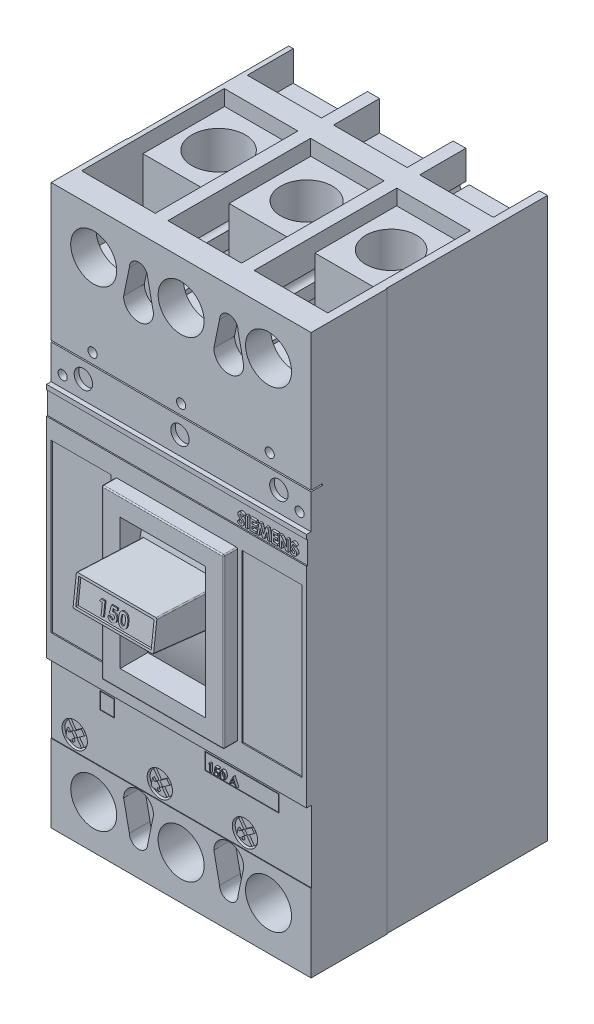
SolidWorks part; units mm, degrees
ref_plane "Alzado" through (0, 0, 0) normal (0, 0, 1) x (1, 0, 0)
ref_plane "Planta" through (0, 0, 0) normal (0, 1, 0) x (1, 0, 0)
ref_plane "Vista lateral" through (0, 0, 0) normal (1, 0, 0) x (0, 0, -1)
sketch "Croquis1" plane through (0, 0, 0) normal (0, 0, 1) x (1, 0, 0)
  line L1 (-56.5, -121.5) -> (56.5, -121.5)
  line L2 (-56.5, -121.5) -> (-56.5, 121.5)
  line L3 (-56.5, 121.5) -> (56.5, 121.5)
  line L4 (56.5, -121.5) -> (56.5, 121.5)
  line L5 (-56.5, -121.5) -> (56.5, 121.5) construction
  line L6 (-56.5, 121.5) -> (56.5, -121.5) construction
  point P0 (0, 0)
  dimension "D1" = 113
  dimension "D2" = 243
extrude "Saliente-Extruir1" add sketch "Croquis1" along normal blind 105
sketch "Croquis2" plane through (0, 0, 105) normal (0, 0, 1) x (1, 0, 0)
  line L0 (56.5, -121.5) -> (56.5, -56.5)
  line L1 (56.5, -121.5) -> (56.5, 121.5) construction
  line L2 (56.5, -56.5) -> (-56.5, -56.5)
  line L3 (-56.5, 121.5) -> (-56.5, -121.5) construction
  line L4 (-56.5, -56.5) -> (-56.5, -121.5)
  line L5 (-56.5, -121.5) -> (56.5, -121.5)
  dimension "D1" = 65
extrude "Cortar-Extruir1" cut sketch "Croquis2" against normal blind 2
sketch "Croquis3" plane through (0, 0, 105) normal (0, 0, 1) x (1, 0, 0)
  line L0 (-56.5, 121.5) -> (-56.5, 46.5)
  line L1 (-56.5, 121.5) -> (-56.5, -56.5) construction
  line L2 (-56.5, 46.5) -> (56.5, 46.5)
  line L3 (56.5, -56.5) -> (56.5, 121.5) construction
  line L4 (56.5, 46.5) -> (56.5, 121.5)
  line L5 (56.5, 121.5) -> (-56.5, 121.5)
  dimension "D1" = 75
extrude "Cortar-Extruir2" cut sketch "Croquis3" against normal blind 2
sketch "Croquis4" plane through (0, 0, 105) normal (0, 0, 1) x (1, 0, 0)
  line L0 (56.5, -56.5) -> (56.5, 46.5) construction
  line L1 (-26.5, -46.5) -> (26.5, -46.5)
  line L2 (-26.5, -46.5) -> (-26.5, 26.5)
  line L3 (-26.5, 26.5) -> (26.5, 26.5)
  line L4 (26.5, -46.5) -> (26.5, 26.5)
  line L5 (-26.5, -46.5) -> (26.5, 26.5) construction
  line L6 (-26.5, 26.5) -> (26.5, -46.5) construction
  line L7 (-56.5, 46.5) -> (56.5, 46.5) construction
  line L8 (-56.5, 46.5) -> (-56.5, -56.5) construction
  line L9 (56.5, -56.5) -> (-56.5, -56.5) construction
  point P0 (0, -10)
  dimension "D1" = 30
  dimension "D2" = 20
  dimension "D3" = 30
  dimension "D4" = 10
extrude "Saliente-Extruir2" add sketch "Croquis4" along normal blind 6
sketch "Croquis5" plane through (0, 0, 111) normal (0, 0, 1) x (1, 0, 0)
  line L0 (26.5, -46.5) -> (26.5, 26.5) construction
  line L1 (-18.5, -38.5) -> (18.5, -38.5)
  line L2 (-18.5, -38.5) -> (-18.5, 18.5)
  line L3 (-18.5, 18.5) -> (18.5, 18.5)
  line L4 (18.5, -38.5) -> (18.5, 18.5)
  line L5 (-18.5, -38.5) -> (18.5, 18.5) construction
  line L6 (-18.5, 18.5) -> (18.5, -38.5) construction
  line L7 (26.5, 26.5) -> (-26.5, 26.5) construction
  line L8 (-26.5, 26.5) -> (-26.5, -46.5) construction
  line L9 (-26.5, -46.5) -> (26.5, -46.5) construction
  point P0 (0, -10)
  point P11 (-18.5, -10)
  dimension "D1" = 8
  dimension "D2" = 8
  dimension "D3" = 8
  dimension "D4" = 8
extrude "Cortar-Extruir3" cut sketch "Croquis5" against normal blind 7
sketch "Croquis6" plane through (-18.5, 0, 0) normal (1, 0, 0) x (0, 0, -1)
  line L0 (-104, 18.5) -> (-99, 18.5)
  line L1 (-104, -38.5) -> (-99, -38.5)
  line L2 (-104, 18.5) -> (-106.9692, 18.5)
  line L3 (-106.9692, 18.5) -> (-106.9692, -38.5)
  line L4 (-106.9692, -38.5) -> (-104, -38.5)
  arc A0 (-99, -38.5) -> (-99, 18.5) centre (-20.275, -10) cw
  dimension "D1" = 5
extrude "Cortar-Extruir4" cut sketch "Croquis6" along normal up to surface (37 mm away) up to face at (18.5, -10, 107.5)
sketch "Croquis7" plane through (-18.5, 0, 0) normal (1, 0, 0) x (0, 0, -1)
  line L0 (-102.2276, 7.1359) -> (-131, 8.458)
  line L1 (-111, -46.5) -> (-111, 26.5) construction
  line L2 (-131, 8.458) -> (-132.497, -4.4555)
  line L3 (-132.497, -4.4555) -> (-103.9701, -7.7626)
  arc A0 (-99, 18.5) -> (-99, -38.5) centre (-20.275, -10) ccw construction
  arc A1 (-102.2276, 7.1359) -> (-103.9701, -7.7626) centre (-20.275, -10) ccw
  dimension "D1" = 20
  dimension "D2" = 13
  dimension "D3" = 15
extrude "Saliente-Extruir3" add sketch "Croquis7" along normal up to surface (37 mm away) up to face at (18.5, -10, 106.25)
sketch "Croquis9" plane through (18.5, 0, 0) normal (1, 0, 0) x (0, 0, -1)
  line L0 (-131, 8.458) -> (-102.2276, 7.1359)
  line L1 (-131, 8.458) -> (-132.497, -4.4555)
  line L2 (-132.497, -4.4555) -> (-103.9701, -7.7626)
  arc A0 (-103.9701, -7.7626) -> (-102.2276, 7.1359) centre (-38.2725, -7.8951) cw
extrude "Cortar-Extruir5" cut sketch "Croquis9" against normal blind 1
sketch "Croquis10" plane through (-18.5, 0, 0) normal (-1, 0, 0) x (0, 0, 1)
  line L0 (102.2276, 7.1359) -> (131, 8.458)
  line L1 (131, 8.458) -> (132.497, -4.4555)
  line L2 (132.497, -4.4555) -> (103.9701, -7.7626)
  arc A0 (103.9701, -7.7626) -> (102.2276, 7.1359) centre (38.2725, -7.8951) ccw
extrude "Cortar-Extruir6" cut sketch "Croquis10" against normal blind 1
sketch "Croquis11" plane through (0, 15.0972, 130.2303) normal (0, 0.1152, 0.9933) x (1, 0, 0)
  line L1 (-16.3625, -18.6242) -> (16.3625, -18.6242)
  line L2 (-16.3625, -18.6242) -> (-16.3625, -7.7431)
  line L3 (-16.3625, -7.7431) -> (16.3625, -7.7431)
  line L4 (16.3625, -18.6242) -> (16.3625, -7.7431)
  line L5 (-16.3625, -18.6242) -> (16.3625, -7.7431) construction
  line L6 (-16.3625, -7.7431) -> (16.3625, -18.6242) construction
  point P0 (0, -13.1836)
extrude "Cortar-Extruir7" cut sketch "Croquis11" against normal blind 1
fillet "Redondeo1" radius 0.5 4 edges at (17.5, -6.109, 118.2336) (17.5, 7.7969, 116.6138) (-17.5, -6.109, 118.2336) (-17.5, 7.7969, 116.6138)
sketch "Croquis12" plane through (0, 14.982, 129.237) normal (0, 0.1152, 0.9933) x (1, 0, 0)
  line L0 (-10.1967, -17.2783) -> (10.7691, -17.2783) construction
  text T0 " 150" font "Century Gothic" height in points 22
extrude "Saliente-Extruir4" add sketch "Croquis12" along normal blind 0.5
fillet "Redondeo2" radius 0.5 8 edges at (-26.5, -46.5, 108) (26.5, -46.5, 108) (0, -46.5, 111) (26.5, -10, 111) (26.5, 26.5, 108) (0, 26.5, 111) (-26.5, -10, 111) (-26.5, 26.5, 108)
sketch "Croquis13" plane through (0, 0, 103) normal (0, 0, 1) x (1, 0, 0)
  line L0 (56.5, 121.5) -> (-56.5, 121.5) construction
  line L1 (56.5, 121.5) -> (56.5, -121.5) construction
  line L2 (56.5, 0) -> (-56.5, 0) construction
  line L3 (-56.5, 46.5) -> (-56.5, -56.5) construction
  circle A0 centre (0, 102.5) radius 10
  circle A1 centre (-38, 102.5) radius 10
  circle A2 centre (38, 102.5) radius 10
  circle A3 centre (38, -102.5) radius 10
  circle A4 centre (-38, -102.5) radius 10
  circle A5 centre (0, -102.5) radius 10
  dimension "D1" = 20
  dimension "D3" = 38
  dimension "D4" = 20
  dimension "D7" = 38
  dimension "D8" = 20
  dimension "D2" = 19
  dimension "D5" = 19
  dimension "D6" = 19
extrude "Cortar-Extruir8" cut sketch "Croquis13" against normal blind 39
sketch "Croquis14" plane through (0, 0, 103) normal (0, 0, 1) x (1, 0, 0)
  line L0 (-56.5, 46.5) -> (56.5, 46.5) construction
  line L1 (-56.5, 121.5) -> (-56.5, 46.5) construction
  line L2 (-25, 94.5) -> (-22.5, 106.5)
  line L3 (-12, 94.5) -> (-14.5, 106.5)
  line L4 (14.2234, 94.5) -> (16.7234, 106.5)
  line L5 (24.7234, 106.5) -> (27.2234, 94.5)
  line L6 (56.5, 121.5) -> (56.5, -121.5) construction
  line L7 (56.5, 0) -> (-56.5, 0) construction
  line L8 (-56.5, 46.5) -> (-56.5, -56.5) construction
  line L9 (24.7234, -106.5) -> (27.2234, -94.5)
  line L10 (14.2234, -94.5) -> (16.7234, -106.5)
  line L11 (-12, -94.5) -> (-14.5, -106.5)
  line L12 (-25, -94.5) -> (-22.5, -106.5)
  arc A0 (-25, 94.5) -> (-12, 94.5) centre (-18.5, 94.5) ccw
  arc A1 (14.2234, 94.5) -> (27.2234, 94.5) centre (20.7234, 94.5) ccw
  arc A2 (-14.5, 106.5) -> (-22.5, 106.5) centre (-18.5, 106.5) ccw
  arc A3 (24.7234, 106.5) -> (16.7234, 106.5) centre (20.7234, 106.5) ccw
  arc A4 (24.7234, -106.5) -> (16.7234, -106.5) centre (20.7234, -106.5) cw
  arc A5 (-14.5, -106.5) -> (-22.5, -106.5) centre (-18.5, -106.5) cw
  arc A6 (14.2234, -94.5) -> (27.2234, -94.5) centre (20.7234, -94.5) cw
  arc A7 (-25, -94.5) -> (-12, -94.5) centre (-18.5, -94.5) cw
  dimension "D3" = 48
  dimension "D4" = 13
  dimension "D5" = 13
  dimension "D8" = 8
  dimension "D9" = 8
  dimension "D1" = 48
  dimension "D2" = 38
  dimension "D6" = 12
  dimension "D7" = 12
extrude "Cortar-Extruir9" cut sketch "Croquis14" against normal blind 9
sketch "Croquis15" plane through (0, 0, 94) normal (0, 0, 1) x (1, 0, 0)
  circle A0 centre (-18.5, 94.5) radius 3.5
  circle A1 centre (20.7234, 94.5) radius 3.5
  circle A2 centre (-18.5, 106.5) radius 2.5
  circle A3 centre (20.7234, 106.5) radius 2.5
  dimension "D1" = 7
  dimension "D2" = 7
  dimension "D3" = 5
  dimension "D4" = 5
extrude "Cortar-Extruir10" cut sketch "Croquis15" against normal up to surface (94 mm away) up to face at (0, 0, 0)
sketch "Croquis16" plane through (0, 0, 94) normal (0, 0, 1) x (1, 0, 0)
  circle A0 centre (-18.5, -94.5) radius 3.5
  circle A1 centre (-18.5, -106.5) radius 2.5
  circle A4 centre (20.7234, -94.5) radius 3.5
  circle A5 centre (20.7234, -106.5) radius 2.5
  dimension "D1" = 7
  dimension "D2" = 5
  dimension "D3" = 7
  dimension "D4" = 5
extrude "Cortar-Extruir11" cut sketch "Croquis16" against normal up to surface (94 mm away) up to face at (17.2234, 94.5, 0)
sketch "Croquis17" plane through (0, 0, 103) normal (0, 0, 1) x (1, 0, 0)
  line L0 (-56.5, 121.5) -> (-56.5, 46.5) construction
  line L1 (-56.5, 46.5) -> (56.5, 46.5) construction
  line L2 (56.5, 46.5) -> (56.5, 121.5) construction
  circle A0 centre (-42.5, 54.5) radius 4
  circle A1 centre (-0.5, 54.5) radius 4
  circle A2 centre (42.5, 55.2532) radius 4
  dimension "D1" = 8
  dimension "D4" = 8
  dimension "D6" = 42
  dimension "D7" = 8
  dimension "D2" = 14
  dimension "D3" = 8
  dimension "D5" = 8
  dimension "D8" = 14
extrude "Cortar-Extruir12" cut sketch "Croquis17" against normal blind 2
sketch "Croquis18" plane through (0, 0, 103) normal (0, 0, 1) x (1, 0, 0)
  line L0 (-56.5, 46.5) -> (56.5, 46.5) construction
  line L1 (-56.5, 121.5) -> (-56.5, 46.5) construction
  line L2 (56.5, 46.5) -> (56.5, 121.5) construction
  circle A0 centre (-51.5, 51.5) radius 2
  circle A1 centre (51.5, 51.5) radius 2
  circle A2 centre (0, 66.5) radius 2
  circle A3 centre (38.5, 67.2532) radius 2
  circle A4 centre (-38.5, 66.5) radius 2
  circle A5 centre (-0.5, 54.5) radius 4 construction
  circle A6 centre (42.5, 55.2532) radius 4 construction
  circle A7 centre (-42.5, 54.5) radius 4 construction
  dimension "D1" = 4
  dimension "D2" = 4
  dimension "D4" = 5
  dimension "D7" = 4
  dimension "D8" = 4
  dimension "D9" = 4
  dimension "D10" = 12
  dimension "D11" = 12
  dimension "D13" = 12
  dimension "D14" = 18
  dimension "D3" = 5
  dimension "D5" = 5
  dimension "D6" = 5
  dimension "D12" = 18
extrude "Cortar-Extruir13" cut sketch "Croquis18" against normal blind 10
sketch "Croquis19" plane through (0, 0, 103) normal (0, 0, 1) x (1, 0, 0)
  line L0 (-56.5, 61.5) -> (56.5, 61.5)
  line L1 (-56.5, 121.5) -> (-56.5, 46.5) construction
  line L2 (56.5, 46.5) -> (56.5, 121.5) construction
  line L3 (56.5, 61.5) -> (56.5, 62.1)
  line L4 (56.5, 62.1) -> (-56.5, 62.1)
  line L5 (-56.5, 62.1) -> (-56.5, 61.5)
  dimension "D1" = 15
  dimension "D2" = 0.6
extrude "Cortar-Extruir14" cut sketch "Croquis19" against normal blind 5
sketch "Croquis20" plane through (0, 0, 103) normal (0, 0, 1) x (1, 0, 0)
  line L0 (-56.5, -56.5) -> (-56.5, -121.5) construction
  circle A0 centre (-9.5, -81.5) radius 5.5
  circle A1 centre (27.5, -81.5) radius 5.5
  circle A2 centre (-46.5, -81.5) radius 5.5
  circle A3 centre (-38, -102.5) radius 10 construction
  circle A4 centre (0, -102.5) radius 10 construction
  circle A5 centre (38, -102.5) radius 10 construction
  dimension "D1" = 11
  dimension "D3" = 21
  dimension "D4" = 11
  dimension "D5" = 37
  dimension "D6" = 21
  dimension "D7" = 11
  dimension "D8" = 37
  dimension "D9" = 21
  dimension "D2" = 10
extrude "Cortar-Extruir15" cut sketch "Croquis20" against normal blind 5
sketch "Croquis21" plane through (0, 0, 98) normal (0, 0, 1) x (1, 0, 0)
  circle A0 centre (-46.5, -81.5) radius 5
  circle A1 centre (-9.5, -81.5) radius 5
  circle A2 centre (27.5, -81.5) radius 5
  dimension "D1" = 10
  dimension "D2" = 10
  dimension "D3" = 10
extrude "Saliente-Extruir5" add sketch "Croquis21" along normal blind 4
sketch "Croquis22" plane through (0, 0, 102) normal (0, 0, 1) x (1, 0, 0)
  line L0 (-49.4105, -77.4344) -> (-43.5895, -85.5656) construction
  line L1 (-12.4105, -77.4344) -> (-6.5895, -85.5656) construction
  line L2 (24.5895, -77.4344) -> (30.4105, -85.5656) construction
  line L3 (-49.9553, -77.886) -> (-44.1926, -85.9358)
  line L4 (-48.8074, -77.0642) -> (-43.0447, -85.114)
  line L5 (-12.9553, -77.886) -> (-7.1926, -85.9358)
  line L6 (-11.8074, -77.0642) -> (-6.0447, -85.114)
  line L7 (24.0447, -77.886) -> (29.8074, -85.9358)
  line L8 (25.1926, -77.0642) -> (30.9553, -85.114)
  circle A0 centre (-46.5, -81.5) radius 5 construction
  circle A1 centre (-9.5, -81.5) radius 5 construction
  circle A2 centre (27.5, -81.5) radius 5 construction
  circle A3 centre (27.5, -81.5) radius 5 construction
  circle A7 centre (-46.5, -81.5) radius 5 construction
  arc A8 (-49.9553, -77.886) -> (-48.8074, -77.0642) centre (-46.5, -81.5) cw
  arc A9 (-44.1926, -85.9358) -> (-43.0447, -85.114) centre (-46.5, -81.5) ccw
  circle A12 centre (-9.5, -81.5) radius 5 construction
  arc A13 (-12.9553, -77.886) -> (-11.8074, -77.0642) centre (-9.5, -81.5) cw
  arc A14 (-7.1926, -85.9358) -> (-6.0447, -85.114) centre (-9.5, -81.5) ccw
  arc A15 (24.0447, -77.886) -> (25.1926, -77.0642) centre (27.5, -81.5) cw
  arc A16 (29.8074, -85.9358) -> (30.9553, -85.114) centre (27.5, -81.5) ccw
extrude "Cortar-Extruir16" cut sketch "Croquis22" against normal blind 2
sketch "Croquis23" plane through (0, 0, 102) normal (0, 0, 1) x (1, 0, 0)
  line L0 (-47.7579, -80.9555) -> (-49.0924, -81.9109)
  line L1 (-49.9553, -77.886) -> (-44.1926, -85.9358) construction
  line L2 (-49.0924, -81.9109) -> (-49.8983, -80.7851)
  line L3 (-46.407, -82.8426) -> (-47.7579, -83.8097)
  line L4 (-49.9553, -77.886) -> (-44.1926, -85.9358) construction
  line L5 (-47.7579, -83.8097) -> (-47.0824, -84.7532)
  line L6 (-47.0824, -84.7532) -> (-50.3001, -84.2204)
  line L7 (-50.3001, -84.2204) -> (-49.8983, -80.7851)
  line L8 (-46.61, -80.1338) -> (-43.6216, -77.9944)
  line L9 (-43.0447, -85.114) -> (-48.8074, -77.0642) construction
  line L10 (-43.6216, -77.9944) -> (-42.2707, -79.8814)
  line L11 (-42.2707, -79.8814) -> (-45.2591, -82.0208)
  line L12 (-45.2591, -82.0208) -> (-46.61, -80.1338)
  line L13 (-46.407, -82.8426) -> (-47.7579, -80.9555)
  line L14 (-10.6623, -81.0891) -> (-11.8102, -81.9109)
  line L15 (-12.9553, -77.886) -> (-7.1926, -85.9358) construction
  line L16 (-11.8102, -81.9109) -> (-12.3985, -81.0891)
  line L17 (-9.407, -82.8426) -> (-10.6623, -83.7412)
  line L18 (-12.9553, -77.886) -> (-7.1926, -85.9358) construction
  line L19 (-10.6623, -83.7412) -> (-9.9378, -84.7532)
  line L20 (-9.9378, -84.7532) -> (-13.2729, -84.201)
  line L21 (-13.2729, -84.201) -> (-12.7073, -80.7851)
  line L22 (-12.7073, -80.7851) -> (-12.3985, -81.0891)
  line L23 (-9.5143, -80.2673) -> (-6.4755, -78.0918)
  line L24 (-6.0447, -85.114) -> (-11.8074, -77.0642) construction
  line L25 (-6.4755, -78.0918) -> (-5.1943, -79.8814)
  line L26 (-5.1943, -79.8814) -> (-8.2332, -82.0569)
  line L27 (-6.0447, -85.114) -> (-11.8074, -77.0642) construction
  line L28 (-8.2332, -82.0569) -> (-9.5143, -80.2673)
  line L29 (-9.407, -82.8426) -> (-10.6623, -81.0891)
  line L30 (26.3261, -81.0729) -> (25.0665, -81.9746)
  line L31 (24.0447, -77.886) -> (29.8074, -85.9358) construction
  line L32 (25.0665, -81.9746) -> (24.4849, -81.1621)
  line L33 (27.454, -82.6484) -> (26.1033, -83.6153)
  line L34 (24.0447, -77.886) -> (29.8074, -85.9358) construction
  line L35 (26.1033, -83.6153) -> (26.8154, -84.61)
  line L36 (26.8154, -84.61) -> (23.9977, -84.0073)
  line L37 (23.9977, -84.0073) -> (24.4849, -81.1621)
  line L38 (27.454, -80.2231) -> (30.4311, -78.0918)
  line L39 (30.9553, -85.114) -> (25.1926, -77.0642) construction
  line L40 (30.4311, -78.0918) -> (31.579, -79.6953)
  line L41 (31.579, -79.6953) -> (28.6019, -81.8266)
  line L42 (28.6019, -81.8266) -> (27.454, -80.2231)
  line L43 (27.454, -82.6484) -> (26.3261, -81.0729)
extrude "Saliente-Extruir6" add sketch "Croquis23" along normal blind 1
sketch "Croquis24" plane through (0, 0, 105) normal (0, 0, 1) x (1, 0, 0)
  line L0 (-56.5, 44.5) -> (56.5, 44.5)
  line L1 (-56.5, 46.5) -> (-56.5, -56.5) construction
  line L2 (56.5, -56.5) -> (56.5, 46.5) construction
  line L3 (56.5, 44.5) -> (56.5, 34.5)
  line L4 (56.5, 34.5) -> (-56.5, 34.5)
  line L5 (-56.5, 34.5) -> (-56.5, 44.5)
  line L6 (-56.5, 46.5) -> (56.5, 46.5) construction
  line L7 (28.5, 26.5) -> (54.5, 26.5)
  line L8 (54.5, 26.5) -> (54.5, -46)
  line L9 (54.5, -46) -> (28.5, -46)
  line L10 (28.5, -46) -> (28.5, 26.5)
  line L11 (-28.5, 26.5) -> (-28.5, -46)
  line L12 (-28.5, -46) -> (-54.5, -46)
  line L13 (-54.5, -46) -> (-54.5, 26.5)
  line L14 (-54.5, 26.5) -> (-28.5, 26.5)
  line L15 (-26.5, 26) -> (-26.5, -46) construction
  line L16 (26.5, 26) -> (26.5, -46) construction
  arc A0 (26, -46.5) -> (26.5, -46) centre (26, -46) ccw construction
  dimension "D9" = 0
  dimension "D1" = 2
  dimension "D2" = 10
  dimension "D3" = 2
  dimension "D4" = 0
  dimension "D5" = 0
  dimension "D6" = 2
  dimension "D7" = 2
  dimension "D8" = 2
  dimension "D10" = 0
extrude "Cortar-Extruir17" cut sketch "Croquis24" against normal blind 0.5
sketch "Croquis25" plane through (0, 0, 103) normal (0, 0, 1) x (1, 0, 0)
  line L0 (-56.5, -87.75) -> (56.5, -87.75)
  line L1 (-56.5, -56.5) -> (-56.5, -121.5) construction
  line L2 (56.5, -121.5) -> (56.5, -56.5) construction
  line L3 (-56.5, -121.5) -> (56.5, -121.5) construction
  line L4 (-56.5, -87.75) -> (-56.5, -56.5)
  line L5 (-56.5, -56.5) -> (56.5, -56.5)
  line L6 (56.5, -56.5) -> (56.5, -87.75)
  dimension "D1" = 33.75
extrude "Cortar-Extruir18" cut sketch "Croquis25" against normal blind 0.25
sketch "Croquis26" plane through (56.5, 0, 0) normal (1, 0, 0) x (0, 0, -1)
  line L0 (-70, 121.5) -> (-70, -121.5)
  line L1 (-103, 121.5) -> (0, 121.5) construction
  line L2 (-103, -121.5) -> (0, -121.5) construction
  line L3 (-103, 62.1) -> (-103, 121.5) construction
  line L4 (0, -121.5) -> (0, 121.5) construction
  line L5 (-70, 121.5) -> (0, 121.5)
  line L6 (0, 121.5) -> (0, -121.5)
  line L7 (0, -121.5) -> (-70, -121.5)
  dimension "D1" = 33
  dimension "D2" = 70
extrude "Cortar-Extruir19" cut sketch "Croquis26" against normal blind 0.25
sketch "Croquis28" plane through (-56.5, 0, 0) normal (-1, 0, 0) x (0, 0, 1)
  line L0 (70, 121.5) -> (70, -121.5)
  line L1 (103, -121.5) -> (0, -121.5) construction
  line L2 (70, 121.5) -> (0, 121.5)
  line L3 (0, 121.5) -> (0, -121.5)
  line L4 (0, -121.5) -> (70, -121.5)
extrude "Cortar-Extruir20" cut sketch "Croquis28" against normal blind 0.25
sketch "Croquis29" plane through (0, 0, 102.75) normal (0, 0, 1) x (1, 0, 0)
  line L1 (10.1285, -66.6911) -> (42.3006, -66.6911)
  line L2 (10.1285, -66.6911) -> (10.1285, -59.3793)
  line L3 (10.1285, -59.3793) -> (42.3006, -59.3793)
  line L4 (42.3006, -66.6911) -> (42.3006, -59.3793)
  line L5 (10.1285, -66.6911) -> (42.3006, -59.3793) construction
  line L6 (10.1285, -59.3793) -> (42.3006, -66.6911) construction
  line L7 (-35.4486, -66.6911) -> (-29.1117, -66.6911)
  line L8 (-35.4486, -66.6911) -> (-35.4486, -59.3793)
  line L9 (-35.4486, -59.3793) -> (-29.1117, -59.3793)
  line L10 (-29.1117, -66.6911) -> (-29.1117, -59.3793)
  line L11 (-35.4486, -66.6911) -> (-29.1117, -59.3793) construction
  line L12 (-35.4486, -59.3793) -> (-29.1117, -66.6911) construction
  point P0 (26.2146, -63.0352)
  point P5 (-32.2802, -63.0352)
extrude "Cortar-Extruir21" cut sketch "Croquis29" against normal blind 4
sketch "Croquis30" plane through (0, 0, 98.75) normal (0, 0, 1) x (1, 0, 0)
  line L1 (10.3184, -66.4658) -> (42.1108, -66.4658)
  line L2 (10.3184, -66.4658) -> (10.3184, -59.6046)
  line L3 (10.3184, -59.6046) -> (42.1108, -59.6046)
  line L4 (42.1108, -66.4658) -> (42.1108, -59.6046)
  line L5 (10.3184, -66.4658) -> (42.1108, -59.6046) construction
  line L6 (10.3184, -59.6046) -> (42.1108, -66.4658) construction
  line L7 (-35.2213, -66.4658) -> (-29.3391, -66.4658)
  line L8 (-35.2213, -66.4658) -> (-35.2213, -59.6046)
  line L9 (-35.2213, -59.6046) -> (-29.3391, -59.6046)
  line L10 (-29.3391, -66.4658) -> (-29.3391, -59.6046)
  line L11 (-35.2213, -66.4658) -> (-29.3391, -59.6046) construction
  line L12 (-35.2213, -59.6046) -> (-29.3391, -66.4658) construction
  point P0 (26.2146, -63.0352)
  point P5 (-32.2802, -63.0352)
extrude "Saliente-Extruir7" add sketch "Croquis30" along normal blind 4
sketch "Croquis32" plane through (0, 121.5, 0) normal (0, 1, 0) x (1, 0, 0)
  line L0 (-54.25, -92) -> (-54.25, -30)
  line L1 (-54.25, -92) -> (-22.25, -92)
  line L2 (-22.25, -92) -> (-22.25, -30)
  line L5 (56.5, -103) -> (-56.5, -103) construction
  line L6 (-16.75, -92) -> (-16.75, -30)
  line L7 (-16.75, -92) -> (15.25, -92)
  line L8 (15.25, -92) -> (15.25, -30)
  line L9 (20.75, -92) -> (20.75, -30)
  line L10 (20.75, -92) -> (52.75, -92)
  line L11 (52.75, -92) -> (52.75, -30)
  line L12 (-54.25, -30) -> (-22.25, -30)
  line L13 (15.25, -30) -> (-16.75, -30)
  line L14 (52.75, -30) -> (20.75, -30)
  dimension "D1" = 32
  dimension "D3" = 11
  dimension "D4" = 32
  dimension "D5" = 5.5
  dimension "D6" = 32
  dimension "D9" = 62
  dimension "D10" = 62
  dimension "D12" = 62
extrude "Cortar-Extruir22" cut sketch "Croquis32" against normal blind 32
sketch "Croquis33" plane through (0, 121.5, 0) normal (0, 1, 0) x (1, 0, 0)
  line L0 (-54.25, -20) -> (-22, -20)
  line L1 (-22, 0) -> (-22, -94) construction
  line L2 (-22, -20) -> (-22, 0)
  line L3 (-22, 0) -> (-54.25, 0)
  line L4 (56.25, 0) -> (-56.25, 0) construction
  line L5 (-54.25, 0) -> (-54.25, -20)
  line L6 (-22.25, -30) -> (-54.25, -30) construction
  line L7 (-16.75, -20) -> (15.25, -20)
  line L8 (15.25, -20) -> (15.25, 0)
  line L9 (15.25, 0) -> (-16.75, 0)
  line L10 (-16.75, 0) -> (-16.75, -20)
  line L11 (52.75, -20) -> (20.75, -20)
  line L12 (20.75, -20) -> (20.75, 0)
  line L13 (20.75, 0) -> (52.75, 0)
  line L14 (52.75, 0) -> (52.75, -20)
  dimension "D1" = 10
extrude "Cortar-Extruir24" cut sketch "Croquis33" against normal blind 13
sketch "Croquis34" plane through (0, 89.5, 0) normal (0, 1, 0) x (1, 0, 0)
  line L1 (-53.3865, -66.2346) -> (-23.1135, -66.2346)
  line L2 (-53.3865, -66.2346) -> (-53.3865, -30.6996)
  line L3 (-53.3865, -30.6996) -> (-23.1135, -30.6996)
  line L4 (-23.1135, -66.2346) -> (-23.1135, -30.6996)
  line L5 (-53.3865, -66.2346) -> (-23.1135, -30.6996) construction
  line L6 (-53.3865, -30.6996) -> (-23.1135, -66.2346) construction
  line L7 (-15.9234, -66.2346) -> (14.4234, -66.2346)
  line L8 (-15.9234, -66.2346) -> (-15.9234, -30.6996)
  line L9 (-15.9234, -30.6996) -> (14.4234, -30.6996)
  line L10 (14.4234, -66.2346) -> (14.4234, -30.6996)
  line L11 (-15.9234, -66.2346) -> (14.4234, -30.6996) construction
  line L12 (-15.9234, -30.6996) -> (14.4234, -66.2346) construction
  line L13 (21.3905, -66.2346) -> (52.1095, -66.2346)
  line L14 (21.3905, -66.2346) -> (21.3905, -30.6996)
  line L15 (21.3905, -30.6996) -> (52.1095, -30.6996)
  line L16 (52.1095, -66.2346) -> (52.1095, -30.6996)
  line L17 (21.3905, -66.2346) -> (52.1095, -30.6996) construction
  line L18 (21.3905, -30.6996) -> (52.1095, -66.2346) construction
  point P0 (-38.25, -48.4671)
  point P5 (-0.75, -48.4671)
  point P10 (36.75, -48.4671)
extrude "Saliente-Extruir8" add sketch "Croquis34" along normal blind 26
sketch "Croquis35" plane through (0, 115.5, 0) normal (0, 1, 0) x (1, 0, 0)
  circle A0 centre (-38.25, -48.4671) radius 11.6277
  circle A1 centre (0, -48.4671) radius 11.2451
  circle A2 centre (36.75, -48.4671) radius 11.0163
extrude "Cortar-Extruir25" cut sketch "Croquis35" against normal blind 26
sketch "Croquis36" plane through (0, -121.5, 0) normal (0, -1, 0) x (1, 0, 0)
  line L0 (-54.25, 25) -> (-54.25, 87)
  line L1 (-54.25, 87) -> (-24.25, 87)
  line L2 (-56.25, 0) -> (-56.25, 70) construction
  line L3 (-56.5, 103) -> (56.5, 103) construction
  line L4 (-24.25, 87) -> (-24.25, 25)
  line L5 (-24.25, 25) -> (-54.25, 25)
  line L6 (-15.25, 87) -> (-15.25, 25)
  line L7 (-15.25, 87) -> (14.75, 87)
  line L8 (14.75, 87) -> (14.75, 25)
  line L9 (14.75, 25) -> (-15.25, 25)
  line L10 (23.75, 87) -> (23.75, 25)
  line L11 (23.75, 25) -> (53.75, 25)
  line L12 (53.75, 25) -> (53.75, 87)
  line L13 (53.75, 87) -> (23.75, 87)
  dimension "D1" = 2
  dimension "D2" = 16
  dimension "D3" = 62
  dimension "D4" = 30
  dimension "D5" = 9
  dimension "D6" = 30
  dimension "D7" = 9
  dimension "D8" = 30
extrude "Cortar-Extruir26" cut sketch "Croquis36" against normal blind 32
sketch "Croquis37" plane through (0, -121.5, 0) normal (0, -1, 0) x (1, 0, 0)
  line L0 (-54.25, 15.6798) -> (-24.25, 15.6798)
  line L1 (-24.25, 15.6798) -> (-24.25, 0)
  line L2 (-56.25, 0) -> (56.25, 0) construction
  line L3 (-24.25, 0) -> (-54.25, 0)
  line L4 (-54.25, 0) -> (-54.25, 15.6798)
  line L5 (-15.25, 15.6798) -> (-15.25, 0)
  line L6 (-15, 0) -> (14.75, 0)
  line L7 (14.75, 0) -> (14.75, 15.6798)
  line L8 (-15.25, 0) -> (-15, 0)
  line L9 (14.75, 15.6798) -> (-15.25, 15.6798)
  line L10 (23.75, 15.6798) -> (23.75, 0)
  line L11 (23.75, 0) -> (53.75, 0)
  line L12 (53.75, 0) -> (53.75, 15.6798)
  line L13 (53.75, 15.6798) -> (23.75, 15.6798)
extrude "Cortar-Extruir27" cut sketch "Croquis37" against normal blind 13
sketch "Croquis38" plane through (0, 0, 102.75) normal (0, 0, 1) x (1, 0, 0)
  line L0 (11.9519, -65.5389) -> (28.5263, -65.5389) construction
  text T0 "150 A"
extrude "Saliente-Extruir9" add sketch "Croquis38" along normal blind 1
sketch "Croquis39" plane through (0, 0, 104.5) normal (0, 0, 1) x (1, 0, 0)
  line L0 (26.7106, 36.2281) -> (55.7643, 36.2281) construction
  text T0 "SIEMENS" font "Century Gothic" height in points 18
extrude "Saliente-Extruir10" add sketch "Croquis39" along normal blind 1
sketch "Croquis40" plane through (0, -89.5, 0) normal (0, -1, 0) x (1, 0, 0)
  line L1 (14.612, 60.3193) -> (-15.112, 60.3193)
  line L2 (14.612, 60.3193) -> (14.612, 25.1481)
  line L3 (14.612, 25.1481) -> (-15.112, 25.1481)
  line L4 (-15.112, 60.3193) -> (-15.112, 25.1481)
  line L5 (14.612, 60.3193) -> (-15.112, 25.1481) construction
  line L6 (14.612, 25.1481) -> (-15.112, 60.3193) construction
  line L7 (-53.9054, 60.3193) -> (-24.5946, 60.3193)
  line L8 (-53.9054, 60.3193) -> (-53.9054, 25.1481)
  line L9 (-53.9054, 25.1481) -> (-24.5946, 25.1481)
  line L10 (-24.5946, 60.3193) -> (-24.5946, 25.1481)
  line L11 (-53.9054, 60.3193) -> (-24.5946, 25.1481) construction
  line L12 (-53.9054, 25.1481) -> (-24.5946, 60.3193) construction
  line L13 (53.4816, 60.3193) -> (24.0184, 60.3193)
  line L14 (53.4816, 60.3193) -> (53.4816, 25.1481)
  line L15 (53.4816, 25.1481) -> (24.0184, 25.1481)
  line L16 (24.0184, 60.3193) -> (24.0184, 25.1481)
  line L17 (53.4816, 60.3193) -> (24.0184, 25.1481) construction
  line L18 (53.4816, 25.1481) -> (24.0184, 60.3193) construction
  point P0 (-0.25, 42.7337)
  point P5 (-39.25, 42.7337)
  point P10 (38.75, 42.7337)
extrude "Saliente-Extruir11" add sketch "Croquis40" along normal blind 26
sketch "Croquis41" plane through (0, -115.5, 0) normal (0, -1, 0) x (1, 0, 0)
  circle A0 centre (38.75, 42.7337) radius 11.9915
  circle A1 centre (0, 42.7337) radius 12.2778
  circle A2 centre (-39.25, 42.7337) radius 12.6909
extrude "Cortar-Extruir28" cut sketch "Croquis41" against normal blind 26
